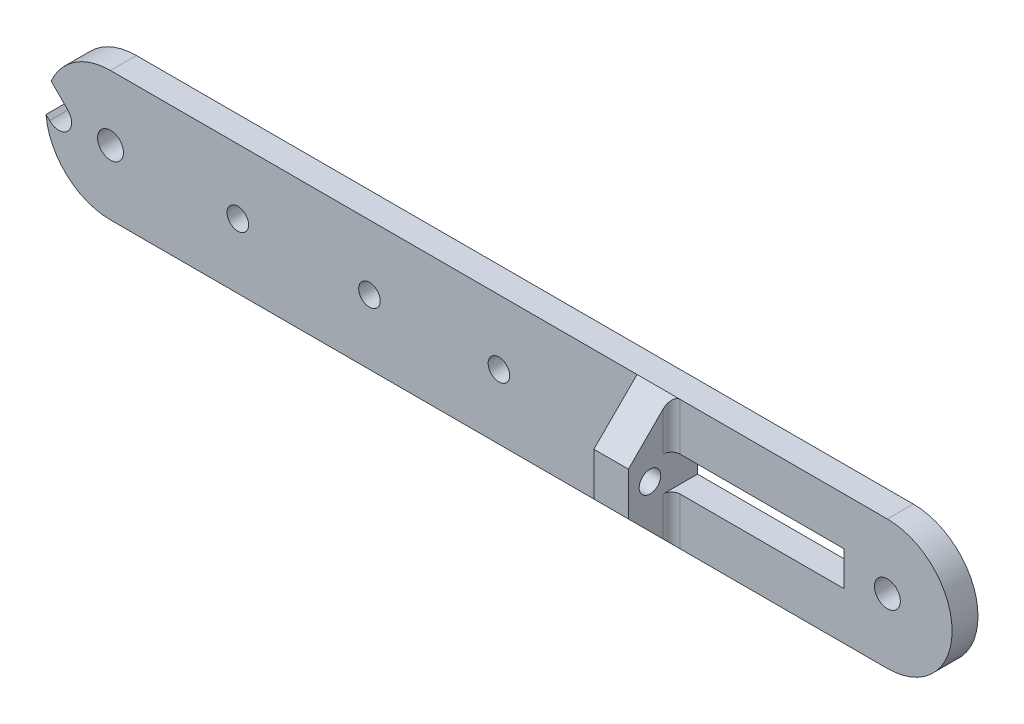
SolidWorks part; units mm, degrees
ref_plane "Plan de face" through (0, 0, 0) normal (0, 0, 1) x (1, 0, 0)
ref_plane "Plan de dessus" through (0, 0, 0) normal (0, 1, 0) x (1, 0, 0)
ref_plane "Plan de droite" through (0, 0, 0) normal (1, 0, 0) x (0, 0, -1)
sketch "Esquisse1" plane through (0, 0, 0) normal (0, 0, 1) x (1, 0, 0)
  line L0 (-74.3787, 0) -> (69.7437, 0) construction
  line L1 (0, 0) -> (0, 19.0596) construction
  line L2 (90, -15) -> (-90, -15)
  line L3 (90, 15) -> (-90, 15)
  line L5 (40, -4) -> (80, -4)
  line L6 (40, -4) -> (40, 4)
  line L7 (40, 4) -> (80, 4)
  line L8 (80, -4) -> (80, 4)
  line L9 (40, -4) -> (80, 4) construction
  line L10 (40, 4) -> (80, -4) construction
  arc A0 (90, -15) -> (90, 15) centre (90, 0) ccw
  circle A1 centre (90, 0) radius 3
  circle A2 centre (-90, 0) radius 3
  arc A3 (-90, -15) -> (-90, 15) centre (-90, 0) cw
  circle A4 centre (0, 0) radius 2.5
  circle A5 centre (-60.5, 0) radius 2.5
  circle A6 centre (-30, 0) radius 2.5
  point P4 (60, 0)
  point P17 (0, -15)
  point P20 (0, 15)
  dimension "D1" = 30
  dimension "D3" = 6
  dimension "D7" = 5
  dimension "D8" = 5
  dimension "D9" = 5
  dimension "D10" = 60.5
  dimension "D2" = 90
  dimension "D4" = 8
  dimension "D5" = 40
  dimension "D6" = 60
  dimension "D11" = 30
extrude "Boss.-Extru.1" add sketch "Esquisse1" along normal blind 6
sketch "Esquisse2" plane through (40, 0, 0) normal (1, 0, 0) x (0, 0, -1)
  line L0 (0, -4) -> (-6, 4) construction
  line L1 (-6, 4) -> (-6, 0) construction
  line L2 (-6, 4) -> (-6, -4) construction
  line L3 (-6, 0) -> (-15.5036, 0) construction
  line L4 (-6, 15) -> (-6, -15) construction
  line L6 (-16, 5) -> (-16, -5)
  line L8 (-6, 5) -> (-6, -5)
  line L9 (-16, 5) -> (-6, -5) construction
  line L10 (-16, -5) -> (-6, 5) construction
  line L11 (-6, -15) -> (-16, -5)
  line L12 (-6, -15) -> (-6, -5)
  line L13 (-6, 5) -> (-6, 15)
  line L14 (-6, 15) -> (-16, 5)
  circle A0 centre (-11, 0) radius 2.5
  point P7 (-11, 0)
  dimension "D3" = 5
  dimension "D1" = 10
  dimension "D2" = 10
extrude "Boss.-Extru.2" add sketch "Esquisse2" against normal blind 8
fillet "Congé2" radius 2 2 edges
sketch "Esquisse3" plane through (32, 0, 0) normal (-1, 0, 0) x (0, 0, 1)
  line L0 (11, 0) -> (11, 4) construction
  line L1 (11, 0) -> (14.4641, 2) construction
  line L2 (11, 0) -> (14.4641, -2) construction
  line L3 (11, 4) -> (14.4641, 2)
  line L4 (14.4641, 2) -> (14.4641, -2)
  line L5 (14.4641, -2) -> (11, -4)
  line L6 (7.5359, 2) -> (7.5359, -2)
  line L7 (11, 4) -> (7.5359, 2)
  line L8 (7.5359, -2) -> (11, -4)
  dimension "D2" = 60
  dimension "D3" = 60
extrude "Enlèv. mat.-Extru.1" cut sketch "Esquisse3" against normal blind 4
sketch "Esquisse4" plane through (0, 0, 6) normal (0, 0, 1) x (1, 0, 0)
  line L0 (-90, 0) -> (-105, 0) construction
  line L1 (-105, 0) -> (-102, 0) construction
  line L2 (-102, 0) -> (-104.1213, -2.1213) construction
  line L3 (-104.1213, -2.1213) -> (-99.8787, 2.1213)
  line L4 (-104.1213, -2.1213) -> (-99.8787, 2.1213)
  line L5 (-104.1213, -2.1213) -> (-108.504, 2.2614)
  line L6 (-99.8787, 2.1213) -> (-104.2614, 6.504)
  line L7 (-108.504, 2.2614) -> (-104.2614, 6.504)
  arc A0 (-90, 15) -> (-90, -15) centre (-90, 0) ccw construction
  circle A1 centre (-102, 0) radius 3
  arc M9 (-90, 15) -> (-90, -15) centre (-90, 0) ccw
  dimension "D1" = 3
  dimension "D2" = 45
extrude "Enlèv. mat.-Extru.4" cut sketch "Esquisse4" against normal blind 10 contours L3 A1 | A1 L6 M9 | A1 L5 M9 | L3 A1 region at (-102.9003, 0.9003, 6) region at (-101.0997, -0.9003, 6) region at (-104.7977, -1.1965, 6) region at (-103.2777, 3.6386, 6)
